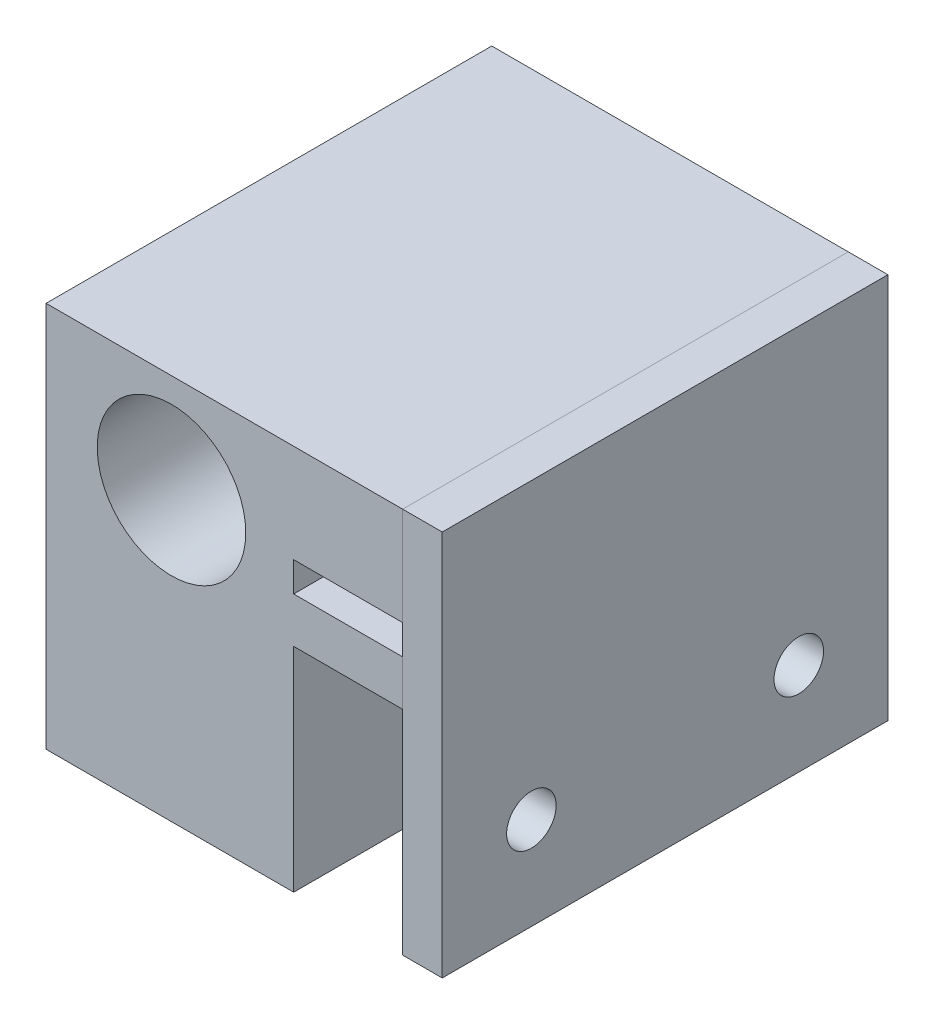
SolidWorks part; units mm, degrees
ref_plane "Front Plane" through (0, 0, 0) normal (0, 0, 1) x (1, 0, 0)
ref_plane "Top Plane" through (0, 0, 0) normal (0, 1, 0) x (1, 0, 0)
ref_plane "Right Plane" through (0, 0, 0) normal (1, 0, 0) x (0, 0, -1)
sketch "Sketch1" plane through (0, 0, 0) normal (0, 0, 1) x (1, 0, 0)
  line L5 (20, 29) -> (-20, 29)
  line L6 (20, 29) -> (20, -10)
  line L7 (20, -10) -> (-20, -10)
  line L8 (-20, 29) -> (-20, -10)
  line L9 (20, 29) -> (-20, -10) construction
  line L10 (20, -10) -> (-20, 29) construction
  circle A0 centre (-7.34, 19) radius 7.5
  point P0 (0, 9.5)
  dimension "D3" = 15
  dimension "D1" = 40
  dimension "D2" = 39
  dimension "D4" = 10
  dimension "D5" = 27.34
extrude "Boss-Extrude1" add sketch "Sketch1" against normal blind 45
sketch "Sketch3" plane through (0, -10, 0) normal (0, -1, 0) x (1, 0, 0)
  line L0 (-7.34, -0.349) -> (-7.34, -3.737) construction
  line L1 (-20, -45) -> (20, -45) construction
  line L2 (-7.34, 0) -> (-7.34, -45) construction
  line L3 (-20, 0) -> (20, 0) construction
  line L5 (-14.84, -0.349) -> (0.16, -0.349) construction
  circle A0 centre (-7.34, -11.25) radius 4
  circle A1 centre (-7.34, -33.75) radius 4
  point P5 (13.75, 0)
  dimension "D5" = 8
  dimension "D1" = 11.25
extrude "Cut-Extrude1" cut sketch "Sketch3" against normal blind 17
sketch "Sketch5" plane through (0, 0, -45) normal (0, 0, -1) x (-1, 0, 0)
  line L0 (-5, -10) -> (-5, 11.5)
  line L1 (20, -10) -> (-20, -10) construction
  line L3 (-16, 11.5) -> (-16, -10)
  line L4 (-16, -10) -> (-5, -10)
  line L5 (-20, -10) -> (-20, 29) construction
  line L7 (53, 9) -> (-447, 9) construction
  line L9 (-16, 19) -> (-5, 19) construction
  line L11 (-447, 19) -> (53, 19) construction
  line L12 (-16, 11.5) -> (-5, 11.5)
  line L13 (-16, 16.08) -> (-5, 16.08)
  line L14 (-16, 16.08) -> (-16, 19.08)
  line L15 (-16, 19.08) -> (-5, 19.08)
  line L16 (-5, 19.08) -> (-5, 16.08)
  dimension "D1" = 25
  dimension "D2" = 4
  dimension "D3" = 2.5
  dimension "D4" = 7.08
  dimension "D5" = 3
extrude "Cut-Extrude3" cut sketch "Sketch5" against normal through all
sketch "Sketch6" plane through (20, 0, 0) normal (1, 0, 0) x (0, 0, -1)
  line L1 (45, -10) -> (45, 29) construction
  line L2 (0, -10) -> (0, 29) construction
  line L6 (-259.5137, 9) -> (160.4863, 9) construction
  circle A0 centre (36, -0.65) radius 2.5
  circle A3 centre (9, -0.65) radius 2.5
  dimension "D2" = 5
  dimension "D3" = 9
  dimension "D4" = 9
  dimension "D1" = 9.65
extrude "Cut-Extrude4" cut sketch "Sketch6" against normal up to surface (4 mm away) up to face at (16, 0.75, -22.5)
ref_plane "Plane1" through (16, 0, 0) normal (-1, 0, 0) x (0, 0, 1)
split "Split1" trim tools "Plane1" bodies to split 105 resulting bodies 106 107
